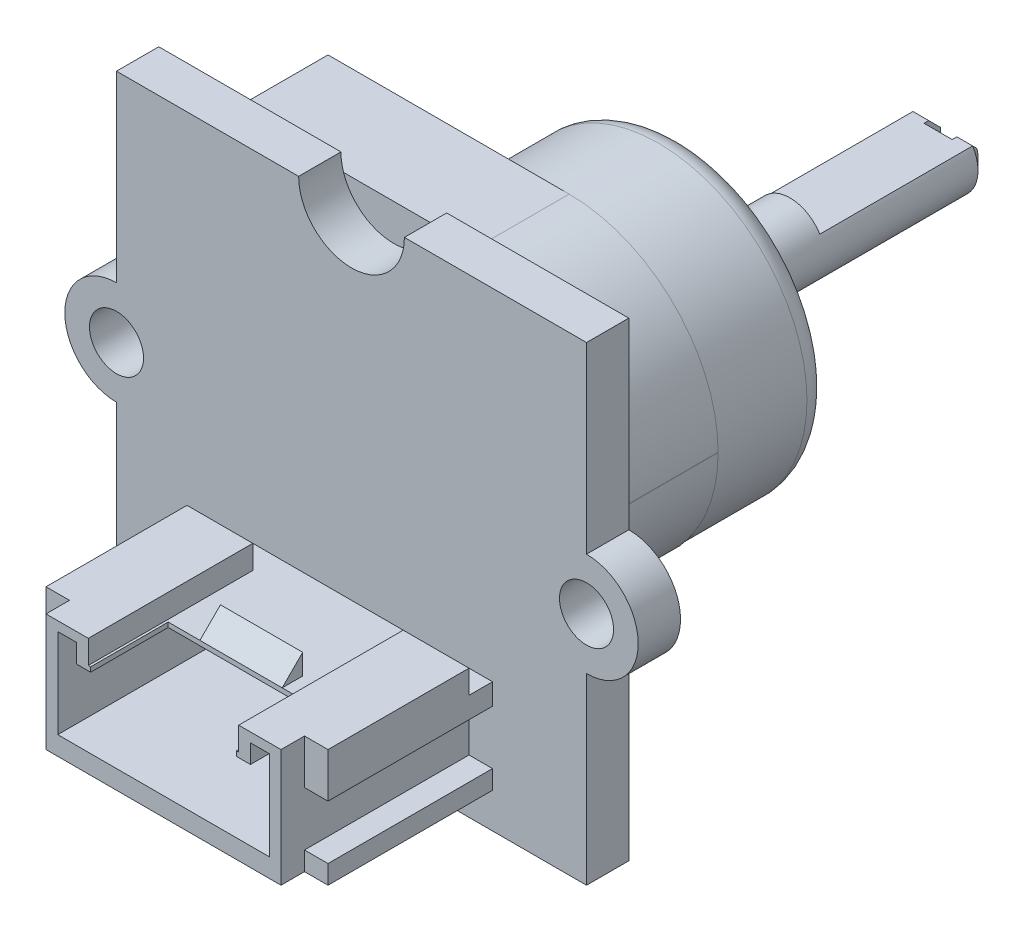
SolidWorks part; units mm, degrees
ref_plane "Plan de face" through (0, 0, 0) normal (0, 0, 1) x (1, 0, 0)
ref_plane "Plan de dessus" through (0, 0, 0) normal (0, 1, 0) x (1, 0, 0)
ref_plane "Plan de droite" through (0, 0, 0) normal (1, 0, 0) x (0, 0, -1)
sketch "Esquisse1" plane through (0, 0, 0) normal (0, 0, 1) x (1, 0, 0)
  line L0 (-2.7446, 10.9929) -> (-2.7446, -9.0071) construction
  line L1 (-12.7446, 10.9929) -> (-4.9946, 10.9929)
  line L2 (-12.7446, 10.9929) -> (-12.7446, 3.1929)
  line L3 (-12.7446, -9.0071) -> (-4.9946, -9.0071)
  line L4 (7.2554, 10.9929) -> (7.2554, 3.1929)
  line L5 (-12.7446, 0.9929) -> (7.2554, 0.9929) construction
  line L6 (-0.4946, 10.9929) -> (7.2554, 10.9929)
  line L7 (-0.4946, -9.0071) -> (7.2554, -9.0071)
  line L8 (-12.7446, -1.2071) -> (-12.7446, -9.0071)
  line L9 (7.2554, -1.2071) -> (7.2554, -9.0071)
  arc A0 (-4.9946, 10.9929) -> (-0.4946, 10.9929) centre (-2.7446, 10.9929) ccw
  arc A1 (-0.4946, -9.0071) -> (-4.9946, -9.0071) centre (-2.7446, -9.0071) ccw
  arc A2 (-12.7446, 3.1929) -> (-12.7446, -1.2071) centre (-12.7446, 0.9929) ccw
  arc A3 (7.2554, -1.2071) -> (7.2554, 3.1929) centre (7.2554, 0.9929) ccw
  circle A4 centre (-12.7446, 0.9929) radius 1.15
  circle A5 centre (7.2554, 0.9929) radius 1.15
  dimension "D1" = 20
  dimension "D2" = 20
extrude "Boss.-Extru.1" add sketch "Esquisse1" along normal blind 1.8
sketch "Esquisse2" plane through (0, 0, 1.8) normal (0, 0, 1) x (1, 0, 0)
  line L0 (-12.7446, -1.2071) -> (-12.7446, -9.0071) construction
  line L1 (-8.7446, -7.5071) -> (3.2554, -7.5071)
  line L2 (-8.7446, -7.5071) -> (-8.7446, -6.7071)
  line L3 (-8.7446, -2.5071) -> (3.2554, -2.5071)
  line L4 (3.2554, -7.5071) -> (3.2554, -6.7071)
  line L5 (-12.7446, -9.0071) -> (-4.9946, -9.0071) construction
  line L6 (3.2554, -4.4071) -> (2.2554, -4.4071)
  line L7 (-8.7446, -4.4071) -> (-7.7446, -4.4071)
  line L9 (-8.7446, -6.7071) -> (-7.7446, -6.7071)
  line L10 (-7.7446, -4.4071) -> (-7.7446, -6.7071)
  line L11 (2.2554, -4.4071) -> (2.2554, -6.7071)
  line L12 (2.2554, -6.7071) -> (3.2554, -6.7071)
  line L13 (-8.7446, -4.4071) -> (-8.7446, -2.5071)
  line L14 (3.2554, -4.4071) -> (3.2554, -2.5071)
  dimension "D1" = 12
  dimension "D2" = 5
  dimension "D3" = 4
  dimension "D4" = 1.5
  dimension "D5" = 1.9
  dimension "D6" = 1
  dimension "D7" = 2.3
extrude "Boss.-Extru.2" add sketch "Esquisse2" along normal blind 8
sketch "Esquisse3" plane through (0, 0, 9.8) normal (0, 0, 1) x (1, 0, 0)
  line L0 (-8.7446, -7.5071) -> (3.2554, -7.5071) construction
  line L1 (-6.4446, -3.7071) -> (0.9554, -3.7071)
  line L2 (-7.2446, -3.7071) -> (-7.2446, -6.7071)
  line L3 (-7.2446, -6.7071) -> (1.7554, -6.7071)
  line L4 (1.7554, -3.7071) -> (1.7554, -6.7071)
  line L5 (-7.7446, -4.4071) -> (-7.7446, -6.7071) construction
  line L6 (-7.2446, -3.7071) -> (-7.2446, -2.9071)
  line L7 (-7.2446, -2.9071) -> (-6.4446, -2.9071)
  line L8 (-6.4446, -2.9071) -> (-6.4446, -3.7071)
  line L9 (1.7554, -3.7071) -> (1.7554, -2.9071)
  line L10 (1.7554, -2.9071) -> (0.9554, -2.9071)
  line L11 (0.9554, -2.9071) -> (0.9554, -3.7071)
  dimension "D1" = 3
  dimension "D2" = 0.8
  dimension "D3" = 9
  dimension "D4" = 0.5
extrude "Enlèv. mat.-Extru.1" cut sketch "Esquisse3" against normal blind 7
sketch "Esquisse4" plane through (0, -2.5071, 0) normal (0, 1, 0) x (1, 0, 0)
  line L0 (-8.7446, -1.8) -> (3.2554, -1.8)
  line L1 (3.2554, -1.8) -> (3.2554, -2.8)
  line L2 (3.2554, -9.8) -> (3.2554, -1.8) construction
  line L3 (3.2554, -2.8) -> (0.4554, -2.8)
  line L4 (-8.7446, -1.8) -> (-8.7446, -2.8)
  line L5 (-8.7446, -9.8) -> (-8.7446, -1.8) construction
  line L6 (-8.7446, -2.8) -> (-5.9446, -2.8)
  line L7 (-5.9446, -2.8) -> (-5.9446, -9.8)
  line L8 (3.2554, -9.8) -> (-8.7446, -9.8) construction
  line L9 (0.4554, -2.8) -> (0.4554, -9.8)
  line L10 (0.4554, -9.8) -> (-5.9446, -9.8)
  line L11 (-2.7446, -9.8) -> (-2.7446, -3.7286) construction
  line L13 (-4.4946, -5.6264) -> (-0.9946, -5.6264)
  line L14 (-4.4946, -5.6264) -> (-4.4946, -6.5)
  line L15 (-4.4946, -6.5) -> (-0.9946, -6.5)
  line L16 (-0.9946, -5.6264) -> (-0.9946, -6.5)
  point P22 (-4.4946, -6.0632)
  dimension "D1" = 3.3
  dimension "D2" = 3.5
  dimension "D3" = 1.75
  dimension "D4" = 2.8
  dimension "D5" = 2.8
extrude "Enlèv. mat.-Extru.2" cut sketch "Esquisse4" against normal blind 1
sketch "Esquisse5" plane through (0, -2.5071, 0) normal (0, 1, 0) x (1, 0, 0)
  line L0 (-8.7446, -9.8) -> (-8.7446, -2.8) construction
  line L1 (-8.7446, -9.8) -> (-7.7446, -9.8)
  line L2 (-8.7446, -9.8) -> (-8.7446, -8.8)
  line L3 (-8.7446, -8.8) -> (-7.7446, -8.8)
  line L4 (-7.7446, -9.8) -> (-7.7446, -8.8)
  line L5 (-5.9446, -9.8) -> (-8.7446, -9.8) construction
  line L7 (3.2554, -9.8) -> (2.2554, -9.8)
  line L8 (3.2554, -9.8) -> (3.2554, -8.8)
  line L9 (3.2554, -8.8) -> (2.2554, -8.8)
  line L10 (2.2554, -9.8) -> (2.2554, -8.8)
  dimension "D1" = 1
  dimension "D2" = 1
  dimension "D3" = 1
extrude "Enlèv. mat.-Extru.3" cut sketch "Esquisse5" against normal blind 11
sketch "Esquisse6" plane through (0, -3.5071, 0) normal (0, 1, 0) x (1, 0, 0)
  line L0 (-5.9446, -9.8) -> (0.4554, -9.8) construction
  line L1 (-5.8446, -9.8) -> (0.3554, -9.8)
  line L2 (-5.8446, -9.8) -> (-5.8446, -6.5)
  line L3 (-5.8446, -6.5) -> (0.3554, -6.5)
  line L4 (0.3554, -9.8) -> (0.3554, -6.5)
  line L5 (-8.7446, -8.8) -> (-8.7446, -2.8) construction
  dimension "D1" = 6.2
  dimension "D2" = 2.9
  dimension "D3" = 3.3
extrude "Enlèv. mat.-Extru.4" cut sketch "Esquisse6" against normal blind 1
chamfer "Chanfrein1" distance 1 angle 45 1 edges at (-2.7446, -2.5071, 6.5)
sketch "Esquisse7" plane through (0, 0, 0) normal (0, 0, -1) x (-1, 0, 0)
  line L0 (12.7446, 10.9929) -> (12.7446, 3.1929) construction
  line L1 (9.5446, 10.2929) -> (-0.7154, 10.2929)
  line L2 (9.5446, 10.2929) -> (9.5446, -2.4071)
  line L3 (9.5446, -2.4071) -> (-0.7154, -2.4071)
  line L4 (-7.0554, 3.9529) -> (-7.0554, 3.9329)
  line L5 (0.4946, -9.0071) -> (-7.2554, -9.0071) construction
  arc A0 (-0.7154, -2.4071) -> (-7.0554, 3.9329) centre (-0.7154, 3.9329) cw
  arc A1 (-0.7154, 10.2929) -> (-7.0554, 3.9529) centre (-0.7154, 3.9529) ccw
  point P10 (-7.0554, -2.4071)
  dimension "D5" = 6.34
  dimension "D1" = 12.7
  dimension "D2" = 16.6
  dimension "D3" = 3.2
  dimension "D4" = 6.6
extrude "Boss.-Extru.3" add sketch "Esquisse7" along normal blind 4
sketch "Esquisse8" plane through (0, 0, -4) normal (0, 0, -1) x (-1, 0, 0)
  circle A0 centre (-0.7154, 3.9529) radius 6.32
extrude "Boss.-Extru.4" add sketch "Esquisse8" along normal blind 4.8
fillet "Congé1" radius 1 1 edges at (-5.6046, 3.9529, -8.8)
sketch "Esquisse10" plane through (0, 0, -8.8) normal (0, 0, -1) x (-1, 0, 0)
  circle A0 centre (-0.7154, 3.9529) radius 1.75
extrude "Boss.-Extru.5" add sketch "Esquisse10" along normal blind 1.6
fillet "Congé2" radius 1 1 edges at (-1.0346, 3.9529, -8.8)
sketch "Esquisse11" plane through (0, 0, -10.4) normal (0, 0, -1) x (-1, 0, 0)
  circle A0 centre (-0.7154, 3.9529) radius 1.5
extrude "Boss.-Extru.6" add sketch "Esquisse11" along normal blind 10
sketch "Esquisse12" plane through (0, 0, -20.4) normal (0, 0, -1) x (-1, 0, 0)
  line L0 (-8.242, 4.7529) -> (13.7736, 4.7529) construction
  line L2 (-1.9842, 4.7529) -> (0.9061, 4.7529)
  line L3 (-1.9842, 4.7529) -> (-1.9842, 5.8484)
  line L4 (-1.9842, 5.8484) -> (0.9061, 5.8484)
  line L5 (0.9061, 4.7529) -> (0.9061, 5.8484)
  circle A0 centre (-0.7154, 3.9529) radius 1.5 construction
  dimension "D1" = 0.8
extrude "Enlèv. mat.-Extru.7" cut sketch "Esquisse12" against normal blind 7
chamfer "Chanfrein2" distance 0.5 angle 45 2 edges at (0.7154, 2.4529, -20.4) (0.7154, 4.7529, -20.4)
sketch "Esquisse13" plane through (0, 0, -20.4) normal (0, 0, -1) x (-1, 0, 0)
  line L1 (-1.3154, 4.9291) -> (-0.1154, 4.9291)
  line L2 (-1.3154, 4.9291) -> (-1.3154, 2.1018)
  line L3 (-1.3154, 2.1018) -> (-0.1154, 2.1018)
  line L4 (-0.1154, 4.9291) -> (-0.1154, 2.1018)
  arc A0 (-1.6693, 4.2529) -> (0.2386, 4.2529) centre (-0.7154, 3.9529) ccw construction
  dimension "D1" = 1.2
  dimension "D2" = 0.6
extrude "Enlèv. mat.-Extru.8" cut sketch "Esquisse13" against normal blind 0.7
sketch "Esquisse14" plane through (0, 0, 1.8) normal (0, 0, 1) x (1, 0, 0)
  line L1 (-12.7446, 10.9929) -> (7.2554, 10.9929) construction
  line L2 (-12.7446, 10.9929) -> (-12.7446, -9.0071) construction
  dimension "D1" = 20
  dimension "D2" = 20
sketch "Esquisse15" plane through (0, 0, -19.7) normal (0, 0, -1) x (-1, 0, 0)
  line L0 (-0.7154, 4.7529) -> (-0.7154, 2.4529) construction
  line L1 (-1.9842, 4.7529) -> (0.5535, 4.7529) construction
  arc A0 (-1.3154, 2.5781) -> (-0.1154, 2.5781) centre (-0.7154, 3.9529) ccw construction
  dimension "D1" = 2.3
